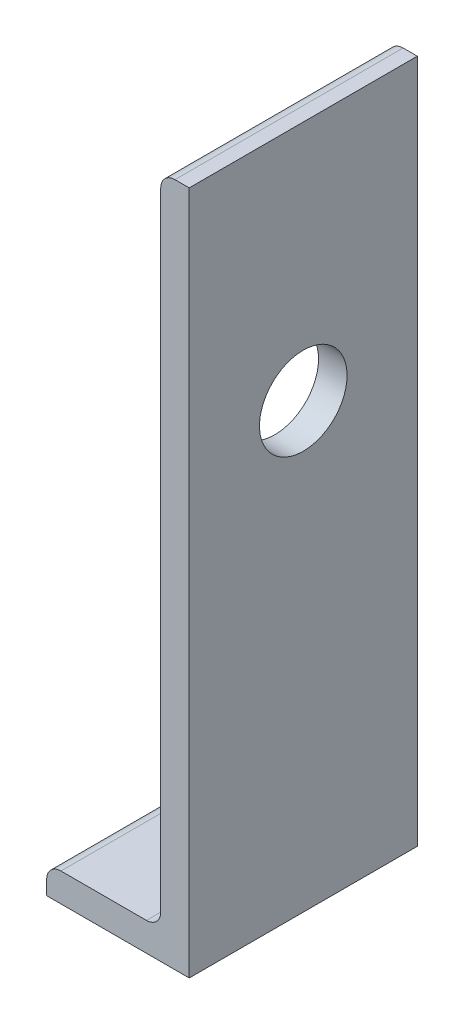
SolidWorks part; units mm, degrees
ref_plane "Front Plane" through (0, 0, 0) normal (0, 0, 1) x (1, 0, 0)
ref_plane "Top Plane" through (0, 0, 0) normal (0, 1, 0) x (1, 0, 0)
ref_plane "Right Plane" through (0, 0, 0) normal (1, 0, 0) x (0, 0, -1)
sketch "Sketch2" plane through (0, 0, 0) normal (0, 0, 1) x (1, 0, 0)
  line L0 (-15.875, 0) -> (15.875, 0)
  line L1 (15.875, 0) -> (15.875, 152.4)
  line L2 (15.875, 152.4) -> (9.525, 152.4) construction
  line L3 (9.525, 149.225) -> (9.525, 9.525)
  line L4 (6.35, 6.35) -> (-12.7, 6.35)
  line L5 (-15.875, 0) -> (-15.875, 6.35) construction
  line L6 (12.7, 152.4) -> (15.875, 152.4)
  line L7 (-15.875, 3.175) -> (-15.875, 0)
  arc A0 (9.525, 149.225) -> (12.7, 152.4) centre (12.7, 149.225) cw
  arc A1 (-15.875, 3.175) -> (-12.7, 6.35) centre (-12.7, 3.175) cw
  arc A2 (9.525, 9.525) -> (6.35, 6.35) centre (6.35, 9.525) cw
  dimension "Vert" = 152.4
  dimension "Horz" = 31.75
  dimension "Thickness" = 6.35
extrude "Boss-Extrude1" add sketch "Sketch2" along normal mid plane 50.8
ref_plane "Contact Plane 1" through (0, 6.35, 0) normal (0, 1, 0) x (1, 0, 0)
ref_plane "Contact Plane 2" through (9.525, 0, 0) normal (-1, 0, 0) x (0, 0, 1)
sketch "Sketch3" plane through (0, 0, 0) normal (0, -1, 0) x (1, 0, 0)
  line L0 (15.875, 0) -> (-15.875, 0) construction
  line L1 (15.875, 25.4) -> (15.875, -25.4) construction
  line L2 (-15.875, 25.4) -> (-15.875, -25.4) construction
  circle A0 centre (-4.826, 0) radius 4.765
  dimension "D1" = 9.53
  dimension "D2" = 20.701
extrude "Cut-Extrude1" cut sketch "Sketch3" against normal through all contours A0
sketch "Sketch4" plane through (15.875, 0, 0) normal (1, 0, 0) x (0, 0, -1)
  line L0 (-25.4, 0) -> (-25.4, 152.4) construction
  circle A1 centre (0, 98.65) radius 9.75
  dimension "D1" = 25.4
  dimension "D2" = 19.5
  dimension "D3" = 98.65
extrude "Cut-Extrude2" cut sketch "Sketch4" against normal blind 12.7
